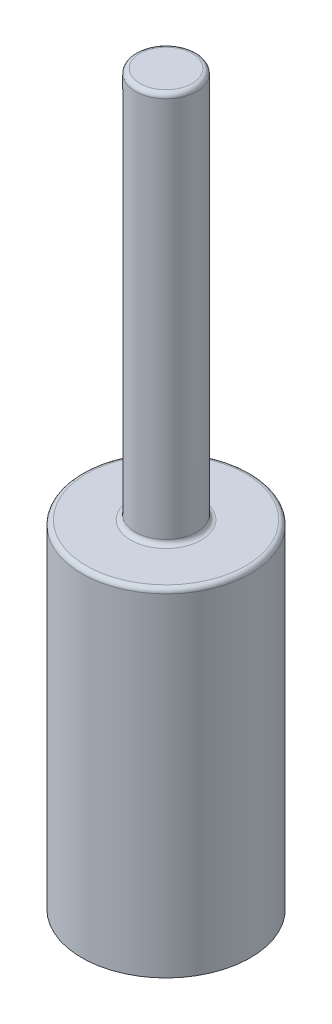
SolidWorks part; units mm, degrees
ref_plane "Front Plane" through (0, 0, 0) normal (0, 0, 1) x (1, 0, 0)
ref_plane "Top Plane" through (0, 0, 0) normal (0, 1, 0) x (1, 0, 0)
ref_plane "Right Plane" through (0, 0, 0) normal (1, 0, 0) x (0, 0, -1)
sketch "Sketch1" plane through (0, 0, 0) normal (0, 1, 0) x (1, 0, 0)
  circle A0 centre (0, 0) radius 2
  dimension "D1" = 4
extrude "Boss-Extrude1" add sketch "Sketch1" against normal blind 11.5
sketch "Sketch3" plane through (0, 0, 0) normal (0, 1, 0) x (1, 0, 0)
  circle A1 centre (0, 0) radius 2
  circle A2 centre (0, 0) radius 2
  dimension "D1" = 0
extrude "Boss-Extrude2" add sketch "Sketch3" along normal blind 14
sketch "Sketch4" plane through (0, -11.5, 0) normal (0, -1, 0) x (1, 0, 0)
  circle A1 centre (0, 0) radius 2
  circle A2 centre (0, 0) radius 2
  dimension "D1" = 0
extrude "Boss-Extrude3" add sketch "Sketch4" along normal blind 24
ref_plane "Plane1" through (0, -33.5, 0) normal (0, -1, 0) x (-1, 0, 0)
sketch "Sketch5" plane through (0, -33.5, 0) normal (0, -1, 0) x (-1, 0, 0)
  circle A0 centre (0, 0) radius 5.5
  dimension "D1" = 11
extrude "Boss-Extrude4" add sketch "Sketch5" against normal blind 22
fillet "Fillet1" radius 0.3 2 edges at (0, 14, 2) (0, -35.5, -2)
fillet "Fillet2" radius 0.3 3 edges at (0, -33.5, -2) (0, -11.5, -2) (0, -11.5, -5.5)
sketch "Sketch6" plane through (0, -33.5, 0) normal (0, -1, 0) x (1, 0, 0)
  circle A0 centre (0, 0) radius 2.85
  circle A1 centre (0, 0) radius 2.7
  dimension "D1" = 5.7
  dimension "D2" = 5.4
extrude "Cut-Extrude1" cut sketch "Sketch6" against normal blind 0.1
fillet "Fillet3" radius 0.3 1 edges at (0, -33.5, -2.7)
sketch "Sketch7" plane through (0, -33.5, 0) normal (0, -1, 0) x (1, 0, 0)
  circle A0 centre (0, 0) radius 5
  circle A1 centre (0, 0) radius 4.5
  dimension "D1" = 10
  dimension "D2" = 9
extrude "Cut-Extrude2" cut sketch "Sketch7" against normal blind 0.3
fillet "Fillet4" radius 0.2 2 edges at (0, -33.5, -4.5) (0, -33.5, -5)
